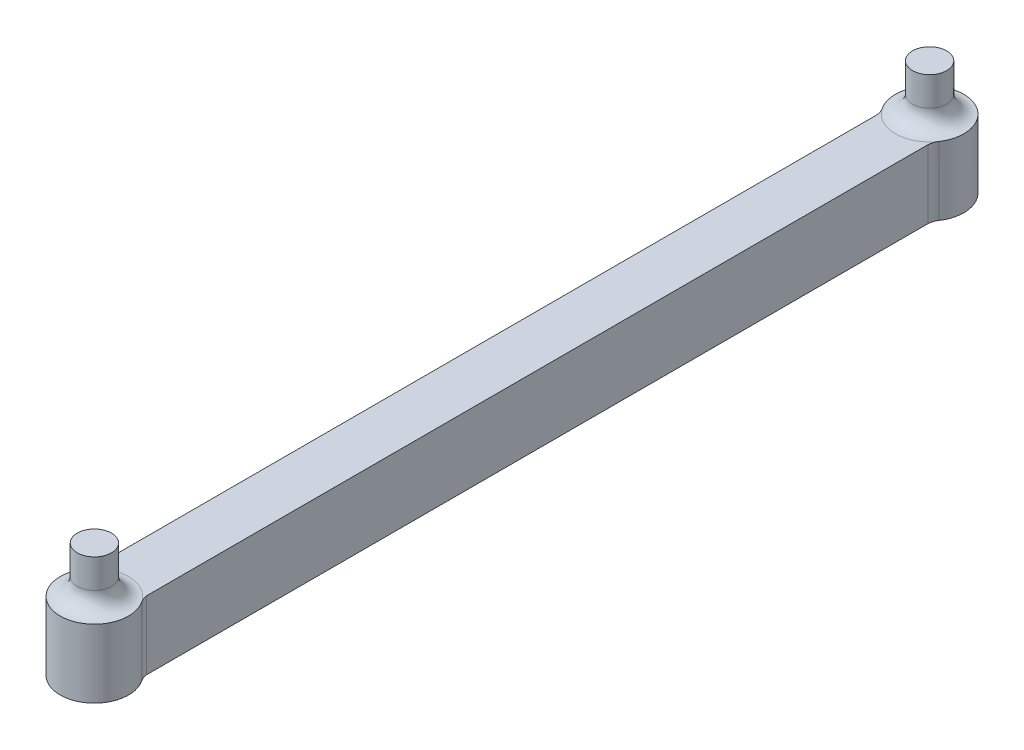
SolidWorks part; units mm, degrees
ref_plane "Ebene vorne" through (0, 0, 0) normal (0, 0, 1) x (1, 0, 0)
ref_plane "Ebene oben" through (0, 0, 0) normal (0, 1, 0) x (1, 0, 0)
ref_plane "Ebene rechts" through (0, 0, 0) normal (1, 0, 0) x (0, 0, -1)
sketch "Skizze1" plane through (0, 0, 0) normal (0, 0, 1) x (1, 0, 0)
  line L1 (-1.5, 2) -> (1.5, 2)
  line L2 (-1.5, 2) -> (-1.5, -2)
  line L3 (-1.5, -2) -> (1.5, -2)
  line L4 (1.5, 2) -> (1.5, -2)
  line L5 (-1.5, 2) -> (1.5, -2) construction
  line L6 (-1.5, -2) -> (1.5, 2) construction
  point P0 (0, 0)
  dimension "D1" = 3
  dimension "D2" = 4
extrude "Aufsatz-Linear austragen1" add sketch "Skizze1" along normal blind 45.7
sketch "Skizze2" plane through (0, 0, 0) normal (0, 1, 0) x (1, 0, 0)
  circle A0 centre (0, -47.238) radius 2
  circle A2 centre (0, 1.5818) radius 2
extrude "Aufsatz-Linear austragen2" add sketch "Skizze2" against normal blind 4 from offset 2
sketch "Skizze3" plane through (0, 2, 0) normal (0, 1, 0) x (1, 0, 0)
  circle A0 centre (0, -47.238) radius 1
  circle A2 centre (0, 1.5818) radius 1
extrude "Aufsatz-Linear austragen4" add sketch "Skizze3" along normal blind 2.7
fillet "Verrundung1" radius 1 4 edges at (-1.2785, 0, 45.7) (1.2785, 0, 45.7) (-1.2239, 0, 0) (1.2239, 0, 0)
fillet "Verrundung2" radius 1 2 edges at (0, 2, -2.5818) (0, 2, 46.238)
